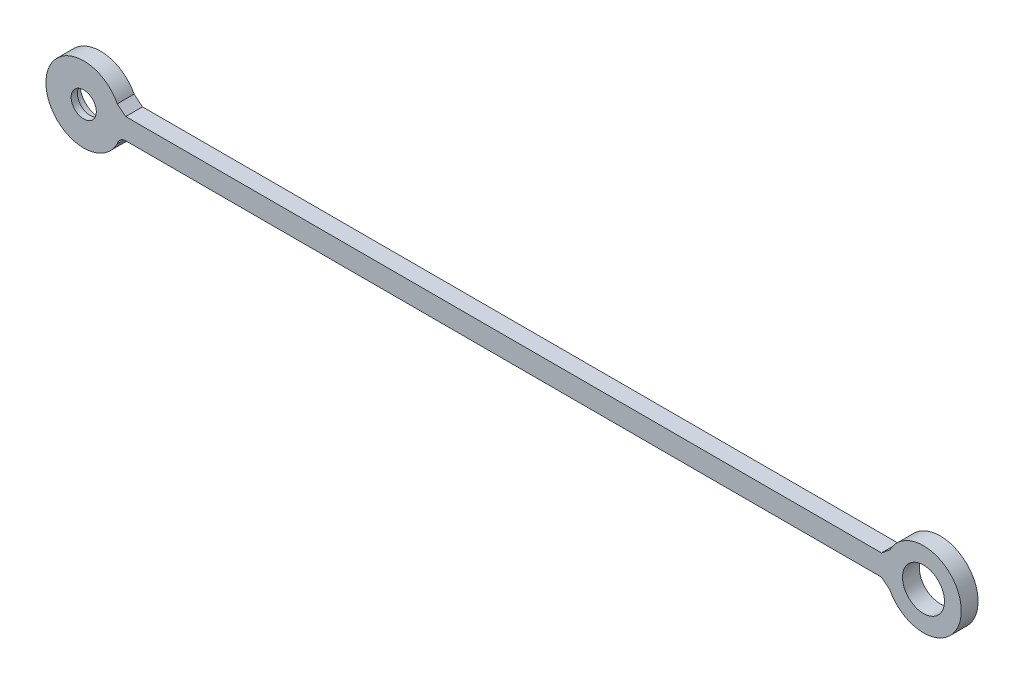
SolidWorks part; units mm, degrees
ref_plane "前视基准面" through (0, 0, 0) normal (0, 0, 1) x (1, 0, 0)
ref_plane "上视基准面" through (0, 0, 0) normal (0, 1, 0) x (1, 0, 0)
ref_plane "右视基准面" through (0, 0, 0) normal (1, 0, 0) x (0, 0, -1)
sketch "草图1" plane through (0, 0, 0) normal (0, 0, 1) x (1, 0, 0)
  line L0 (-95, -1.6682) -> (85, -1.6682)
  line L1 (85, 3.3318) -> (-95, 3.3318)
  line L2 (-118.4836, 0.8318) -> (115.821, 0.8318) construction
  line L3 (-95, 39.4843) -> (-95, -27.8145) construction
  line L4 (85, 39.4843) -> (85, -27.8145) construction
  line L5 (87, 32.5481) -> (87, -23.5765) construction
  line L6 (-97, 33.9202) -> (-97, -30.5192) construction
  line L7 (85, -1.6682) -> (87, -3.2914)
  circle A0 centre (-105, 0.8318) radius 5
  circle A1 centre (-105, 0.8318) radius 3
  circle A2 centre (95, 0.8318) radius 5
  arc A3 (-95, -1.6682) -> (-97, -3.2914) centre (-95, -3.712) ccw
  arc A5 (87, -3.2914) -> (87, 4.9549) centre (95, 0.8318) ccw
  arc A6 (85, 3.3318) -> (87, 4.9549) centre (13.9036, 92.9809) ccw
  arc A7 (-97, 4.9549) -> (-95, 3.3318) centre (-54.4504, 55.341) ccw
  arc A8 (-97, 4.9549) -> (-97, -3.2914) centre (-105, 0.8318) ccw
  dimension "D2" = 10
  dimension "D3" = 6
  dimension "D4" = 10
  dimension "D5" = 9
  dimension "D6" = 9
  dimension "D1" = 0.8318
  dimension "D7" = 2.5
  dimension "D8" = 2.5
  dimension "D9" = 200
  dimension "D12" = 2
  dimension "D14" = 2
extrude "凸台-拉伸1" add sketch "草图1" along normal blind 4 contours A7 L1 A6 A5 L7 L0 A3 A8 | A2 | A1
extrude "切除-拉伸1" cut sketch "草图1<3>" along normal blind 2.5 contours A0
sketch "草图1<3>" plane through (0, 0, 0) normal (0, 0, 1) x (1, 0, 0) same geometry as "草图1"
